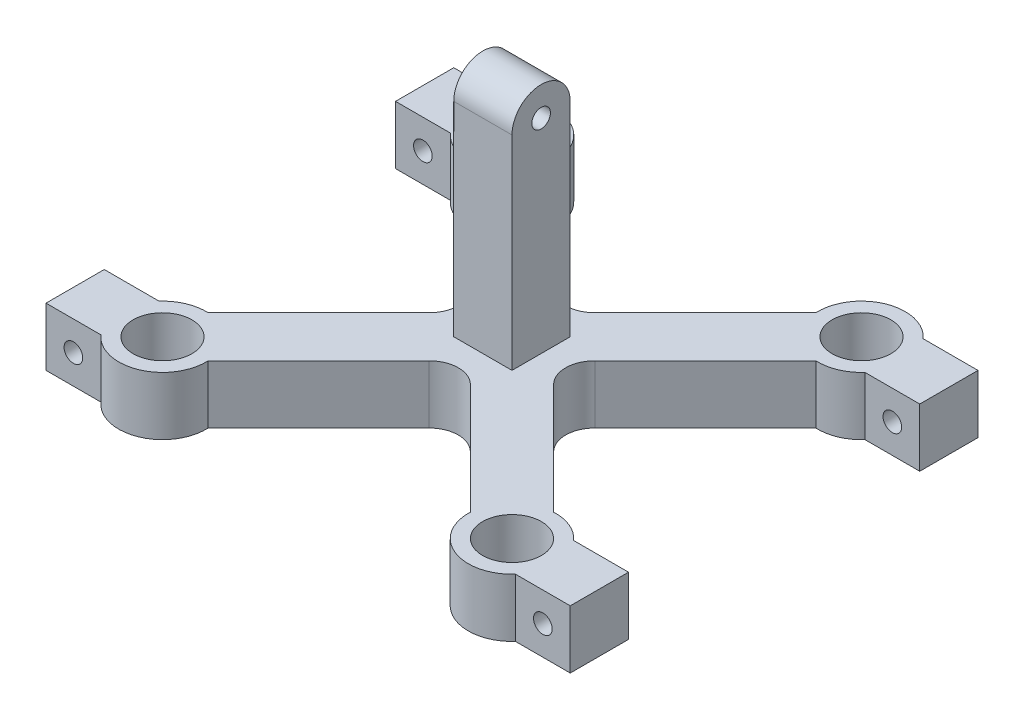
SolidWorks part; units mm, degrees
ref_plane "正面" through (0, 0, 0) normal (0, 0, 1) x (1, 0, 0)
ref_plane "平面" through (0, 0, 0) normal (0, 1, 0) x (1, 0, 0)
ref_plane "右側面" through (0, 0, 0) normal (1, 0, 0) x (0, 0, -1)
sketch "ｽｹｯﾁ1" plane through (0, 0, 0) normal (0, 1, 0) x (1, 0, 0)
  line L0 (0, 0) -> (35355.3391, 35355.3391) construction
  line L1 (-5.5, 0) -> (5.5, 0) construction
  line L2 (3.5355, -10.6773) -> (22.5082, -29.65)
  line L6 (0, 0) -> (35355.3391, -35355.3391) construction
  line L10 (45, -35) -> (35.5902, -35)
  line L29 (35.5902, 25) -> (45, 25)
  line L30 (45, 25) -> (45, 35)
  line L31 (45, 35) -> (35.5902, 35)
  line L32 (3.5355, 10.6773) -> (22.5082, 29.65)
  line L33 (10.6773, 3.5355) -> (29.65, 22.5082)
  line L35 (0, -5.5) -> (0, 5.5) construction
  line L36 (-3.5355, 10.6773) -> (-22.5082, 29.65)
  line L37 (-45, 35) -> (-35.5902, 35)
  line L38 (-45, 25) -> (-45, 35)
  line L39 (-35.5902, 25) -> (-45, 25)
  line L40 (-10.6773, 3.5355) -> (-29.65, 22.5082)
  line L42 (45, -25) -> (45, -35)
  line L43 (35.5902, -25) -> (45, -25)
  line L44 (10.6773, -3.5355) -> (29.65, -22.5082)
  line L47 (-10.6773, -3.5355) -> (-29.65, -22.5082)
  line L48 (-35.5902, -25) -> (-45, -25)
  line L49 (-45, -25) -> (-45, -35)
  line L50 (-45, -35) -> (-35.5902, -35)
  line L51 (-3.5355, -10.6773) -> (-22.5082, -29.65)
  circle A12 centre (30, 30) radius 5.05
  arc A13 (35.5902, 35) -> (22.5082, 29.65) centre (30, 30) ccw
  arc A14 (29.65, 22.5082) -> (35.5902, 25) centre (30, 30) ccw
  circle A15 centre (-30, 30) radius 5.05
  arc A16 (-35.5902, 35) -> (-22.5082, 29.65) centre (-30, 30) cw
  arc A17 (-29.65, 22.5082) -> (-35.5902, 25) centre (-30, 30) cw
  circle A18 centre (30, -30) radius 5.05
  circle A19 centre (-30, -30) radius 5.05
  arc A20 (35.5902, -35) -> (22.5082, -29.65) centre (30, -30) cw
  arc A21 (29.65, -22.5082) -> (35.5902, -25) centre (30, -30) cw
  arc A22 (-29.65, -22.5082) -> (-35.5902, -25) centre (-30, -30) ccw
  arc A23 (-35.5902, -35) -> (-22.5082, -29.65) centre (-30, -30) ccw
  arc A24 (10.6773, 3.5355) -> (10.6773, -3.5355) centre (14.2128, 0) ccw
  arc A25 (-10.6773, -3.5355) -> (-10.6773, 3.5355) centre (-14.2128, 0) ccw
  arc A26 (-3.5355, -10.6773) -> (3.5355, -10.6773) centre (0, -14.2128) cw
  arc A27 (3.5355, 10.6773) -> (-3.5355, 10.6773) centre (0, 14.2128) cw
  dimension "D1" = 45
  dimension "D4" = 10
  dimension "D2" = 10.1
  dimension "D3" = 15
  dimension "D7" = 5
  dimension "D5" = 30
  dimension "D6" = 15
extrude "ﾎﾞｽ - 押し出し1" add sketch "ｽｹｯﾁ1" along normal blind 10
sketch "ｽｹｯﾁ2" plane through (0, 10, 0) normal (0, 1, 0) x (1, 0, 0)
  line L1 (-5, -5) -> (5, -5)
  line L2 (-5, -5) -> (-5, 5)
  line L3 (-5, 5) -> (5, 5)
  line L4 (5, -5) -> (5, 5)
  line L5 (-5, -5) -> (5, 5) construction
  line L6 (-5, 5) -> (5, -5) construction
  point P0 (0, 0)
  dimension "D1" = 10
extrude "ﾎﾞｽ - 押し出し2" add sketch "ｽｹｯﾁ2" along normal blind 40
fillet "ﾌｨﾚｯﾄ3" 2 edges at (0, 50, 5) (0, 50, -5) type full round first side face at (0, 30, 5) second side face at (0, 30, -5) middle face at (0, 50, 0)
sketch "ｽｹｯﾁ3" plane through (5, 0, 0) normal (1, 0, 0) x (0, 0, -1)
  circle A0 centre (0, 45) radius 1.6
  dimension "D1" = 3.2
extrude "ｶｯﾄ - 押し出し1" cut sketch "ｽｹｯﾁ3" against normal through all
sketch "ｽｹｯﾁ4" plane through (0, 0, 35) normal (0, 0, 1) x (1, 0, 0)
  line L0 (-45, 0) -> (-35.5902, 0) construction
  line L1 (-45, 10) -> (-45, 0) construction
  line L2 (45, 10) -> (45, 0) construction
  line L3 (35.5902, 0) -> (45, 0) construction
  circle A0 centre (-40.2951, 5) radius 1.6
  circle A1 centre (40.2951, 5) radius 1.6
  point P4 (0, 0)
  point P7 (-40.2951, 0)
  point P10 (-45, 5)
  point P11 (0, 0)
  point P14 (0, 0)
  point P15 (45, 5)
  point P16 (0, 0)
  point P19 (40.2951, 0)
  dimension "D1" = 3.2
extrude "ｶｯﾄ - 押し出し2" cut sketch "ｽｹｯﾁ4" against normal through all
